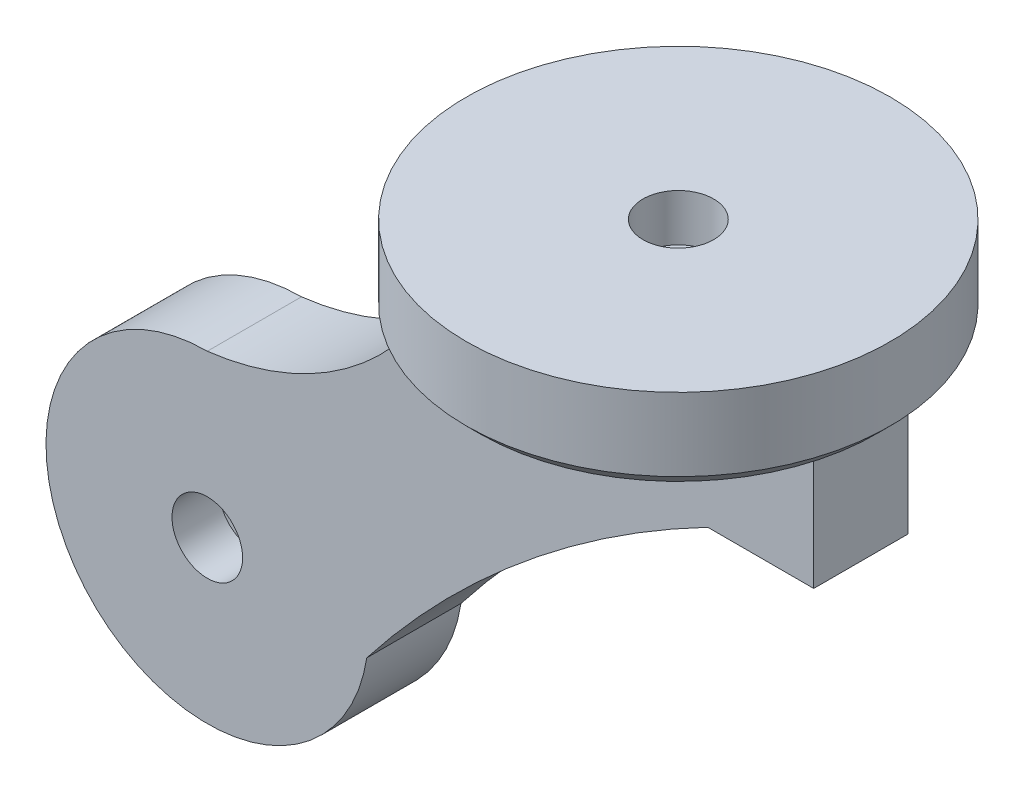
SolidWorks part; units mm, degrees
material "1023 Karbon Çeliği Levha (SS)"
ref_plane "Ön Düzlem" through (0, 0, 0) normal (0, 0, 1) x (1, 0, 0)
ref_plane "Üst Düzlem" through (0, 0, 0) normal (0, 1, 0) x (1, 0, 0)
ref_plane "Sağ Düzlem" through (0, 0, 0) normal (1, 0, 0) x (0, 0, -1)
sketch "Çizim1" plane through (0, 0, 0) normal (0, 1, 0) x (1, 0, 0)
  circle A0 centre (0, 0) radius 90
  dimension "D1" = 180
extrude "Yükseklik-Ekstrüzyon1" add sketch "Çizim1" along normal blind 37
chamfer "Pah1" distance 6 angle 45 1 edges at (0, 0, 90)
sketch "Çizim2" plane through (0, 0, 0) normal (0, -1, 0) x (1, 0, 0)
  line L1 (77.5, -20) -> (-77.5, -20)
  line L2 (77.5, -20) -> (77.5, 20)
  line L3 (77.5, 20) -> (-77.5, 20)
  line L4 (-77.5, -20) -> (-77.5, 20)
  line L5 (77.5, -20) -> (-77.5, 20) construction
  line L6 (77.5, 20) -> (-77.5, -20) construction
  point P0 (0, 0)
  dimension "D1" = 155
  dimension "D2" = 40
extrude "Yükseklik-Ekstrüzyon2" add sketch "Çizim2" along normal blind 50
sketch "Çizim8" plane through (0, 0, -20) normal (0, 0, -1) x (-1, 0, 0)
  line L0 (77.5, -11) -> (77.5, -50)
  line L1 (77.5, -50) -> (77.5, 0) construction
  line L2 (77.5, -50) -> (-32.5, -50)
  line L3 (77.5, -50) -> (-77.5, -50) construction
  arc A0 (77.5, -11) -> (-32.5, -50) centre (68.6761, -160.7402) ccw
  dimension "D2" = 150
  dimension "D1" = 110
extrude "Kes-Ekstrüzyon1" cut sketch "Çizim8" against normal through all
sketch "Çizim11" plane through (0, 0, -20) normal (0, 0, -1) x (-1, 0, 0)
  line L4 (-77.5, -50) -> (-32.5, -50)
  line L5 (77.5, -11) -> (77.5, 0)
  line L6 (77.5, 0) -> (-77.5, 0)
  line L7 (-77.5, 0) -> (-77.5, -50)
  arc A0 (112.294, -170.3991) -> (180, -91.5) centre (180, -160) ccw
  arc A1 (77.5, -11) -> (180, -91.5) centre (194.6346, 32.6404) ccw
  arc A2 (-32.5, -50) -> (112.294, -170.3991) centre (-234.9054, -440.6815) cw
  arc A4 (77.5, -11) -> (-32.5, -50) centre (68.6761, -160.7402) ccw
  arc A5 (77.5, -11) -> (-32.5, -50) centre (68.6761, -160.7402) ccw
  dimension "D2" = 137
  dimension "D4" = 440
  dimension "D5" = 125
  dimension "D1" = 180
  dimension "D3" = 160
  dimension "D6" = 0
extrude "Yükseklik-Ekstrüzyon4" add sketch "Çizim11" against normal blind 40 separate body
sketch "Çizim12" plane through (0, 0, -20) normal (0, 0, -1) x (-1, 0, 0)
  arc A4 (77.5, -11) -> (-32.5, -50) centre (68.6761, -160.7402) ccw
  arc A5 (112.294, -170.3991) -> (-32.5, -50) centre (-234.9054, -440.6815) ccw
  arc A6 (112.294, -170.3991) -> (180, -91.5) centre (180, -160) ccw
  arc A7 (77.5, -11) -> (180, -91.5) centre (194.6346, 32.6404) ccw
  arc A8 (77.5, -11) -> (-32.5, -50) centre (68.6761, -160.7402) ccw
  arc A9 (112.294, -170.3991) -> (-32.5, -50) centre (-234.9054, -440.6815) ccw
  arc A10 (112.294, -170.3991) -> (180, -91.5) centre (180, -160) ccw
  arc A11 (77.5, -11) -> (180, -91.5) centre (194.6346, 32.6404) ccw
  dimension "D1" = 0
extrude "Yükseklik-Ekstrüzyon5" add sketch "Çizim12" along normal blind 7.5 draft 70
sketch "Çizim14" plane through (0, 0, -27.5) normal (0, 0, -1) x (-1, 0, 0)
  circle A0 centre (178.1663, -161.8726) radius 40
  dimension "D1" = 80
extrude "Yükseklik-Ekstrüzyon6" add sketch "Çizim14" along normal blind 3
sketch "Çizim15" plane through (0, 0, -30.5) normal (0, 0, -1) x (-1, 0, 0)
  circle A1 centre (178.1663, -161.8726) radius 40
  circle A2 centre (178.1663, -161.8726) radius 40
  dimension "D1" = 0
extrude "Yükseklik-Ekstrüzyon7" add sketch "Çizim15" along normal blind 18 draft 28
sketch "Çizim16" plane through (0, 0, -48.5) normal (0, 0, -1) x (-1, 0, 0)
  line L0 (178.1663, -192.3018) -> (178.1663, -353.8069) construction
  circle A0 centre (178.1663, -161.8726) radius 40 construction
  arc A1 (173.3625, -201.5831) -> (182.9701, -201.5831) centre (178.1663, -161.8726) ccw
  circle A2 centre (178.1663, -161.8726) radius 30.4292 construction
  arc A4 (178.1663, -192.3018) -> (173.3625, -201.5831) centre (180.405, -199.3443) ccw
  arc A5 (178.1663, -192.3018) -> (182.9701, -201.5831) centre (175.9275, -199.3443) cw
extrude "Kes-Ekstrüzyon2" cut sketch "Çizim16" against normal up to surface (21 mm away) up to face at (-218.1663, -161.8726, -27.5)
sketch "Çizim18" plane through (0, 0, -27.5) normal (0, 0, -1) x (-1, 0, 0)
  line L0 (182.9701, -201.5831) -> (173.3625, -201.5831) construction
  line L1 (173.3625, -201.5831) -> (178.1663, -192.3018) construction
  line L2 (178.1663, -192.3018) -> (178.1663, -201.5831) construction
  arc A0 (182.9701, -201.5831) -> (173.3625, -201.5831) centre (178.1663, -161.8726) ccw construction
  arc A1 (182.9701, -201.5831) -> (173.3625, -201.5831) centre (178.1663, -161.8726) ccw construction
  circle A2 centre (178.1663, -196.9424) radius 1.5
  dimension "D1" = 3
extrude "Kes-Ekstrüzyon3" cut sketch "Çizim18" against normal blind 5
pattern_circular "Dairesel Kaplama1" count 12 over 360 about axis through (-178.1663, -161.8726, 0) along (0, 0, 1) of "Kes-Ekstrüzyon2", "Kes-Ekstrüzyon3"
sketch "Çizim19" plane through (0, 0, -48.5) normal (0, 0, -1) x (-1, 0, 0)
  circle A6 centre (178.1663, -161.8726) radius 22.5
  dimension "D1" = 45
extrude "Kes-Ekstrüzyon5" cut sketch "Çizim19" against normal blind 7.6731 draft 45
sketch "Çizim20" plane through (0, 0, -40.8269) normal (0, 0, -1) x (-1, 0, 0)
  line L0 (178.1663, -161.8726) -> (178.1663, 19.7378) construction
  line L1 (175.1663, -153.9196) -> (171.0451, -143.7194)
  line L2 (181.1663, -153.9196) -> (185.2874, -143.7194)
  arc A0 (185.2874, -143.7194) -> (171.0451, -143.7194) centre (178.1663, -161.8726) ccw
  arc A1 (181.1663, -153.9196) -> (175.1663, -153.9196) centre (178.1663, -161.8726) ccw
  point P7 (178.1663, -161.8726)
  dimension "D1" = 39
  dimension "D2" = 17
  dimension "D3" = 22
  dimension "D4" = 3
extrude "Yükseklik-Ekstrüzyon10" add sketch "Çizim20" along normal blind 4 draft 20
pattern_circular "Dairesel Kaplama2" count 4 over 360 about axis through (-178.1663, -162.8679, 0) along (0, 0, 1) of "Yükseklik-Ekstrüzyon10"
sketch "Çizim26" plane through (0, 0, -40.8269) normal (0, 0, -1) x (-1, 0, 0)
  circle A0 centre (177.1709, -162.8679) radius 11.9466
extrude "Yükseklik-Ekstrüzyon16" add sketch "Çizim26" along normal up to surface (4 mm away) draft 20
sketch "Çizim27" plane through (0, 0, -44.8269) normal (0, 0, -1) x (-1, 0, 0)
  circle A0 centre (177.1709, -162.8679) radius 5
  dimension "D1" = 10
extrude "Kes-Ekstrüzyon6" cut sketch "Çizim27" against normal up to surface (4 mm away) up to face at (-186.7053, -171.4074, -40.8269)
sketch "Çizim28" plane through (0, 0, 20) normal (0, 0, 1) x (1, 0, 0)
  circle A0 centre (-180, -160) radius 15
  dimension "D1" = 30
extrude "Kes-Ekstrüzyon7" cut sketch "Çizim28" against normal blind 20
sketch "Çizim29" plane through (0, 37, 0) normal (0, 1, 0) x (1, 0, 0)
  circle A0 centre (0, 0) radius 15
  dimension "D1" = 30
extrude "Kes-Ekstrüzyon8" cut sketch "Çizim29" against normal blind 20
